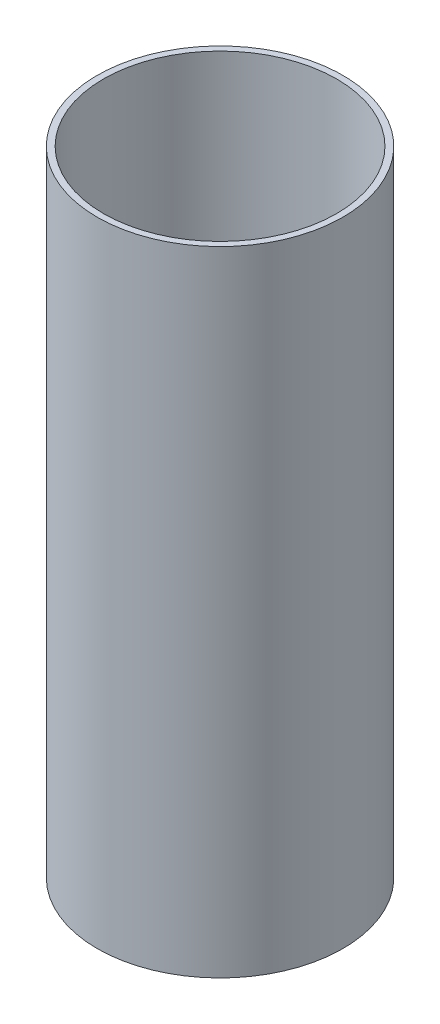
SolidWorks part; units mm, degrees
material "PVC Rigid"
ref_plane "Front Plane" through (0, 0, 0) normal (0, 0, 1) x (1, 0, 0)
ref_plane "Top Plane" through (0, 0, 0) normal (0, 1, 0) x (1, 0, 0)
ref_plane "Right Plane" through (0, 0, 0) normal (1, 0, 0) x (0, 0, -1)
sketch "Sketch1" plane through (0, 0, 0) normal (0, 1, 0) x (1, 0, 0)
  circle A0 centre (0, 0) radius 93.6625
  circle A1 centre (0, 0) radius 88.9
  dimension "D1" = 187.325
  dimension "D2" = 177.8
extrude "Boss-Extrude1" add sketch "Sketch1" along normal mid plane 482.854
ref_plane "Plane1" through (0, 0, 93.6625) normal (0, 0, 1) x (1, 0, 0)
sketch "Sketch3" plane through (0, 0, 93.6625) normal (0, 0, 1) x (1, 0, 0)
  line L0 (0, -55) -> (0, 55) construction
  line L1 (-93.6625, -241.427) -> (93.6625, -241.427) construction
  circle A0 centre (0, -235.077) radius 1.4351
  dimension "D1" = 2.8702
  dimension "D2" = 6.35
extrude "Cut-Extrude1" [suppressed] cut sketch "Sketch3" against normal blind 19.304
pattern_circular "CirPattern1" [suppressed] count 12 over 360 reverse direction yes of bodies 102
mirror "Mirror1" [suppressed] about plane through (0, 0, 0) normal (0, 1, 0)
sketch "Sketch4" [suppressed] plane through (0, 0, 92.075) normal (0, 0, 1) x (1, 0, 0)
  line L0 (0, -55) -> (0, 55) construction
  circle A0 centre (0, -78.359) radius 1.4351
  circle A1 centre (0, 78.359) radius 1.4351
  circle A2 centre (0, 235.077) radius 1.4351 construction
  circle A3 centre (0, -235.077) radius 1.4351 construction
  dimension "D1" = 2.8702
  dimension "D2" = 2.8702
  dimension "D3" = 156.718
  dimension "D4" = 156.718
extrude "Cut-Extrude2" [suppressed] cut sketch "Sketch4" against normal blind 25.146
pattern_circular "CirPattern2" [suppressed] count 3 over 360 of bodies 105
